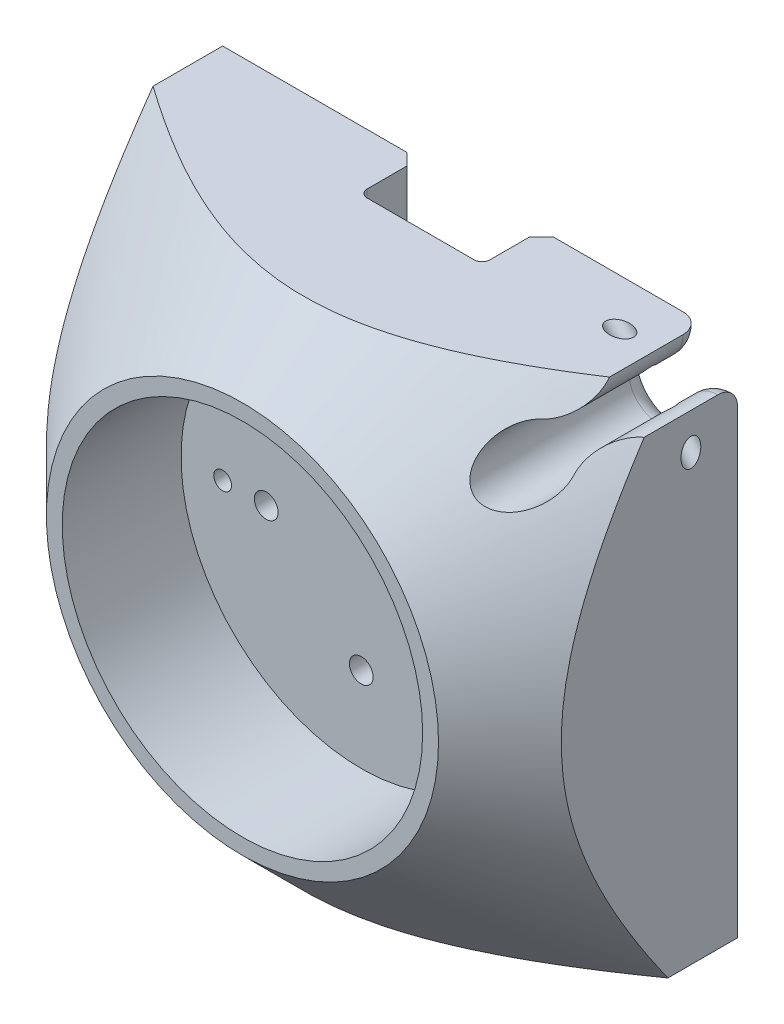
SolidWorks part; units mm, degrees
ref_plane "Top Plane" through (0, 0, 0) normal (0, 0, 1) x (1, 0, 0)
ref_plane "Right Plane" through (0, 0, 0) normal (0, 1, 0) x (1, 0, 0)
ref_plane "Front Plane" through (0, 0, 0) normal (1, 0, 0) x (0, 0, -1)
sketch "Sketch1" plane through (0, 0, 0) normal (0, 0, 1) x (1, 0, 0)
  circle A0 centre (0, 0) radius 45.5
  circle A1 centre (0, 0) radius 49.5
  dimension "D1" = 91
  dimension "D2" = 4
extrude "Boss-Extrude1" add sketch "Sketch1" along normal blind 30
sketch "Sketch2" plane through (0, 0, 0) normal (0, 0, -1) x (-1, 0, 0)
  line L1 (65, 65) -> (-65, 65)
  line L2 (65, 65) -> (65, -65)
  line L3 (65, -65) -> (-65, -65)
  line L4 (-65, 65) -> (-65, -65)
  line L5 (65, 65) -> (-65, -65) construction
  line L6 (65, -65) -> (-65, 65) construction
  point P0 (0, 0)
  dimension "D1" = 130
extrude "Boss-Extrude2" add sketch "Sketch2" along normal blind 15
chamfer "Chamfer1" distance 30 angle 45 1 edges at (49.5, 0, 0)
sketch "Sketch3" plane through (0, 0, 0) normal (0, 1, 0) x (1, 0, 0)
  line L0 (-49.5, -30) -> (-200, 120.5)
  line L1 (-200, 120.5) -> (-200, -30)
  line L2 (-200, -30) -> (-49.5, -30)
  line L5 (0, 0) -> (0, -30) construction
  line L6 (0, -30) -> (-49.5, -30) construction
  dimension "D1" = 200
revolve "Cut-Revolve1" cut sketch "Sketch3" angle 360 about L5
sketch "Sketch4" plane through (0, 0, -15) normal (0, 0, -1) x (-1, 0, 0)
  line L0 (-35, 0) -> (35, 0) construction
  circle A0 centre (0, 0) radius 24 construction
  circle A1 centre (0, -24) radius 3
  circle A2 centre (-24, 0) radius 3
  circle A3 centre (0, 24) radius 3
  circle A4 centre (24, 0) radius 3
  circle A5 centre (-35, 0) radius 2.25
  circle A6 centre (35, 0) radius 2.25
  dimension "D1" = 6
  dimension "D2" = 48
  dimension "D3" = 4.5
  dimension "D4" = 70
extrude "Cut-Extrude1" cut sketch "Sketch4" against normal through all
chamfer "Chamfer2" distance 3 angle 45 2 edges at (21, 0, -15) (-27, 0, -15)
sketch "Sketch5" plane through (0, 0, -15) normal (0, 0, -1) x (-1, 0, 0)
  line L5 (-65, -65) -> (65, -65) construction
  line L6 (-65, 65) -> (-15.5, 65)
  line L7 (-65, 65) -> (-65, -65)
  line L8 (-65, -65) -> (-15.5, -65)
  line L9 (-15.5, 65) -> (-15.5, 13.9553)
  line L11 (15.5, -65) -> (15.5, 65) construction
  line L12 (-15.5, -13.9553) -> (-15.5, -65)
  line L13 (-15.5, 8.4705) -> (-15.5, -8.4705) construction
  line L14 (65, 65) -> (-65, 65) construction
  line L15 (15.5, 65) -> (65, 65) construction
  arc A1 (-19.6, -11.1642) -> (-34.2545, -6.2325) centre (-24, 0) cw
  circle A3 centre (-24, 0) radius 3 construction
  arc A5 (-19.6, -11.1642) -> (-15.5, -13.9553) centre (-18.5, -13.9553) cw
  arc A6 (-19.6, 11.1642) -> (-15.5, 13.9553) centre (-18.5, 13.9553) ccw
  arc A9 (-36.1364, 4.8692) -> (-36.1364, -4.8692) centre (-35, 0) ccw
  circle A10 centre (-35, 0) radius 2.25 construction
  arc A11 (-34.2545, 6.2325) -> (-19.6, 11.1642) centre (-24, 0) cw
  arc A12 (-34.9091, -4.9992) -> (-34.9091, 4.9992) centre (-24, 0) cw construction
  arc A13 (-36.1364, -4.8692) -> (-34.2545, -6.2325) centre (-36.8182, -7.7906) cw
  arc A14 (-36.1364, 4.8692) -> (-34.2545, 6.2325) centre (-36.8182, 7.7906) ccw
  dimension "D2" = 12
  dimension "D3" = 3
  dimension "D4" = 5
  dimension "D5" = 3
  dimension "D1" = 31
extrude "Boss-Extrude3" add sketch "Sketch5" along normal blind 15
mirror "Mirror1" about plane through (0, 0, 0) normal (1, 0, 0) of "Boss-Extrude3"
fillet "Fillet1" radius 2 18 edges at (15.5, 39.4776, -15) (16.8118, 11.4754, -15) (27.8274, -11.3732, -15) (16.8118, -11.4754, -15) (15.5, -39.4776, -15) (27.8274, 11.3732, -15) (35.0581, 5.3612, -15) (40, 0, -15) (35.0581, -5.3612, -15) (-15.5, 39.4776, -15) (-16.8118, 11.4754, -15) (-27.8274, 11.3732, -15) (-35.0581, 5.3612, -15) (-40, 0, -15) (-35.0581, -5.3612, -15) (-27.8274, -11.3732, -15) (-16.8118, -11.4754, -15) (-15.5, -39.4776, -15)
chamfer "Chamfer4" distance 3 angle 45 18 edges at (15.5, 39.4776, -30) (16.8118, 11.4754, -30) (27.8274, -11.3732, -30) (16.8118, -11.4754, -30) (15.5, -39.4776, -30) (27.8274, 11.3732, -30) (35.0581, 5.3612, -30) (40, 0, -30) (35.0581, -5.3612, -30) (-15.5, 39.4776, -30) (-16.8118, 11.4754, -30) (-27.8274, 11.3732, -30) (-35.0581, 5.3612, -30) (-40, 0, -30) (-35.0581, -5.3612, -30) (-27.8274, -11.3732, -30) (-16.8118, -11.4754, -30) (-15.5, -39.4776, -30)
ref_plane "Plane1" through (0, 0, 0) normal (0.7071, -0.7071, 0) x (-0.7071, -0.7071, 0)
sketch "Sketch6" plane through (0, 0, -30) normal (0, 0, -1) x (-1, 0, 0)
  line L0 (-18.5, 65) -> (-65, 65) construction
  line L1 (-65, 50) -> (-50, 50) construction
  line L2 (-65, 65) -> (-65, -65) construction
  line L3 (-50, 50) -> (-50, 65) construction
  line L4 (-65, 56.2225) -> (-56.2225, 56.2225) construction
  line L5 (-56.2225, 56.2225) -> (-56.2225, 65) construction
  line L6 (-50, 50) -> (-65, 65) construction
  line L7 (-56.2225, 65) -> (-65, 65)
  line L8 (-65, 65) -> (-65, 56.2225)
  arc A0 (-57.4704, 49.3341) -> (-49.3341, 57.4704) centre (-50, 50) ccw
  arc A1 (-57.4704, 49.3341) -> (-65, 56.2225) centre (-65, 48.663) ccw
  arc A2 (-49.3341, 57.4704) -> (-56.2225, 65) centre (-48.663, 65) cw
  arc A3 (-50, 57.5) -> (-55.3033, 55.3033) centre (-50, 50) ccw construction
  arc A4 (-55.3033, 55.3033) -> (-57.5, 50) centre (-50, 50) ccw construction
  arc A5 (-49.3341, 57.4704) -> (-50, 57.5) centre (-50, 50) ccw construction
  arc A6 (-57.5, 50) -> (-57.4704, 49.3341) centre (-50, 50) ccw construction
  point P14 (-54.2406, 59.8974)
  point P17 (-59.8974, 54.2406)
  dimension "D2" = 15
  dimension "D1" = 15
  dimension "D3" = 8
extrude "Cut-Extrude2" cut sketch "Sketch6" against normal through all
fillet "Fillet2" radius 5 3 edges at (59.8974, 54.2406, -30) (54.2406, 59.8974, -30) (44.6967, 44.6967, -30)
sketch "Sketch7" plane through (0, 0, 0) normal (0.7071, -0.7071, 0) x (-0.7071, -0.7071, 0)
  line L1 (-85.7172, 6.4416) -> (-85.7172, 25) construction
  line L2 (-85.7172, 6.4416) -> (-85.7172, 30) construction
  line L3 (-85.7172, 30) -> (-80.7172, 30) construction
  line L4 (-82.1817, 30) -> (0, 30) construction
  line L5 (-85.7172, 18.2208) -> (-79.2172, 18.2208) construction
  circle A0 centre (-79.2172, 18.2208) radius 2.5
  point P11 (0, 0)
  point P12 (0, 0)
  point P13 (-80.7172, 18.2208)
  dimension "D1" = 5
  dimension "D2" = 4
extrude "Cut-Extrude3" cut sketch "Sketch7" against normal through all both and the other way through all
